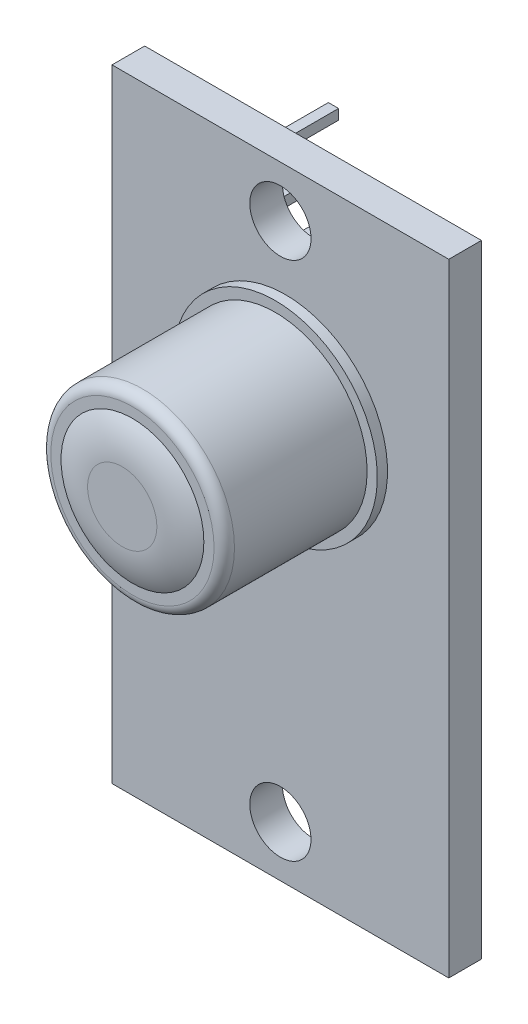
SolidWorks part; units mm, degrees
material "PVC Rigid"
ref_plane "Front Plane" through (0, 0, 0) normal (0, 0, 1) x (1, 0, 0)
ref_plane "Top Plane" through (0, 0, 0) normal (0, 1, 0) x (1, 0, 0)
ref_plane "Right Plane" through (0, 0, 0) normal (1, 0, 0) x (0, 0, -1)
sketch "Sketch1" plane through (0, 0, 0) normal (0, 0, 1) x (1, 0, 0)
  line L0 (0, 15.25) -> (0, 0) construction
  line L1 (-8.25, 15.25) -> (8.25, 15.25)
  line L2 (-8.25, 15.25) -> (-8.25, -15.25)
  line L3 (-8.25, -15.25) -> (8.25, -15.25)
  line L4 (8.25, 15.25) -> (8.25, -15.25)
  line L5 (-8.25, 0) -> (0, 0) construction
  circle A0 centre (0, 12.75) radius 1.5
  circle A1 centre (0, -12.75) radius 1.5
  dimension "D3" = 3
  dimension "D4" = 2.5
  dimension "D1" = 16.5
  dimension "D2" = 30.5
extrude "Extrude1" add sketch "Sketch1" along normal blind 1.6
sketch "Sketch2" plane through (0, 0, 1.6) normal (0, 0, 1) x (1, 0, 0)
  line L0 (0, 12.75) -> (0, -12.75) construction
  line L1 (0, 5.25) -> (0.75, 5.25) construction
  line L2 (8.25, 15.25) -> (-8.25, 15.25) construction
  line L3 (8.25, -15.25) -> (8.25, 15.25) construction
  circle A0 centre (0.75, 5.25) radius 4.5
  dimension "D1" = 9
  dimension "D2" = 10
  dimension "D3" = 7.5
extrude "Extrude2" add sketch "Sketch2" along normal blind 8 from offset 0.5
sketch "Sketch3" plane through (0, 0, 10.1) normal (0, 0, 1) x (1, 0, 0)
  circle A0 centre (0.75, 5.25) radius 4.5 construction
  circle A1 centre (0.75, 5.25) radius 4.5
  circle A2 centre (0.75, 5.25) radius 3.5
  circle A3 centre (0.75, 5.25) radius 3.5
  dimension "D1" = 1
extrude "Cut-Extrude1" cut sketch "Sketch3" against normal blind 0.5
fillet "Fillet2" radius 3.5 1 edges at (4.25, 5.25, 10.1)
fillet "Fillet3" radius 0.5 1 edges at (5.25, 5.25, 9.6)
sketch "Sketch4" plane through (0, 0, 2.1) normal (0, 0, -1) x (-1, 0, 0)
  circle A2 centre (-0.75, 5.25) radius 5
  circle A3 centre (-0.75, 5.25) radius 5
  dimension "D1" = 0.5
extrude "Extrude3" add sketch "Sketch4" against normal blind 0.5
sketch "Sketch5" plane through (0, 0, 0) normal (0, 0, -1) x (-1, 0, 0)
  line L0 (-8.25, 15.25) -> (8.25, 15.25) construction
  line L1 (7.75, 11.75) -> (5.25, 11.75)
  line L2 (7.75, 11.75) -> (7.75, -11.25)
  line L3 (7.75, -11.25) -> (5.25, -11.25)
  line L4 (5.25, 11.75) -> (5.25, -11.25)
  line L5 (8.25, 15.25) -> (8.25, -15.25) construction
  dimension "D1" = 2.5
  dimension "D2" = 23
  dimension "D3" = 3.5
  dimension "D4" = 0.5
extrude "Extrude4" add sketch "Sketch5" along normal blind 1.5
sketch "Sketch6" plane through (0, 0, -1.5) normal (0, 0, -1) x (-1, 0, 0)
  line L0 (6.5, 11.75) -> (6.5, -11.25) construction
  line L1 (7.75, 11.75) -> (5.25, 11.75) construction
  line L2 (5.25, -11.25) -> (7.75, -11.25) construction
  line L3 (6.25, 9.85) -> (6.25, 9.35)
  line L4 (6.25, 9.85) -> (6.75, 9.85)
  line L5 (6.75, 7.45) -> (6.75, 6.95)
  line L6 (6.25, 9.35) -> (6.75, 9.35)
  line L7 (6.75, 9.85) -> (6.75, 9.35)
  line L8 (6.25, 6.95) -> (6.75, 6.95)
  line L9 (6.25, 7.45) -> (6.75, 7.45)
  line L10 (6.25, 7.45) -> (6.25, 6.95)
  line L11 (6.75, 5.05) -> (6.75, 4.55)
  line L12 (6.25, 4.55) -> (6.75, 4.55)
  line L13 (6.25, 5.05) -> (6.75, 5.05)
  line L14 (6.25, 5.05) -> (6.25, 4.55)
  line L15 (6.75, 2.65) -> (6.75, 2.15)
  line L16 (6.25, 2.15) -> (6.75, 2.15)
  line L17 (6.25, 2.65) -> (6.75, 2.65)
  line L18 (6.25, 2.65) -> (6.25, 2.15)
  line L19 (6.75, 0.25) -> (6.75, -0.25)
  line L20 (6.25, -0.25) -> (6.75, -0.25)
  line L21 (6.25, 0.25) -> (6.75, 0.25)
  line L22 (6.25, 0.25) -> (6.25, -0.25)
  line L23 (6.75, -2.15) -> (6.75, -2.65)
  line L24 (6.25, -2.65) -> (6.75, -2.65)
  line L25 (6.25, -2.15) -> (6.75, -2.15)
  line L26 (6.25, -2.15) -> (6.25, -2.65)
  line L27 (6.75, -4.55) -> (6.75, -5.05)
  line L28 (6.25, -5.05) -> (6.75, -5.05)
  line L29 (6.25, -4.55) -> (6.75, -4.55)
  line L30 (6.25, -4.55) -> (6.25, -5.05)
  line L31 (6.75, -6.95) -> (6.75, -7.45)
  line L32 (6.25, -7.45) -> (6.75, -7.45)
  line L33 (6.25, -6.95) -> (6.75, -6.95)
  line L34 (6.25, -6.95) -> (6.25, -7.45)
  line L35 (6.75, -9.35) -> (6.75, -9.85)
  line L36 (6.25, -9.85) -> (6.75, -9.85)
  line L37 (6.25, -9.35) -> (6.75, -9.35)
  line L38 (6.25, -9.35) -> (6.25, -9.85)
  line L39 (6.75, 7.45) -> (6.75, 9.35) construction
  point P8 (6.5, 9.85)
  point P12 (6.5, 9.35)
  dimension "D1" = 0.5
  dimension "D2" = 0.5
  dimension "D3" = 1.9
  dimension "D4" = 1.9
extrude "Extrude5" add sketch "Sketch6" along normal blind 6
ref_axis "Axis1" through (0.75, 5.25, 9.1) along (0, 0, -1)
ref_plane "Plane1" through (0.75, 0, 0) normal (-1, 0, 0) x (0, 0, 1)
ref_plane "Plane2" through (0, 5.25, 0) normal (0, 1, 0) x (-1, 0, 0)
